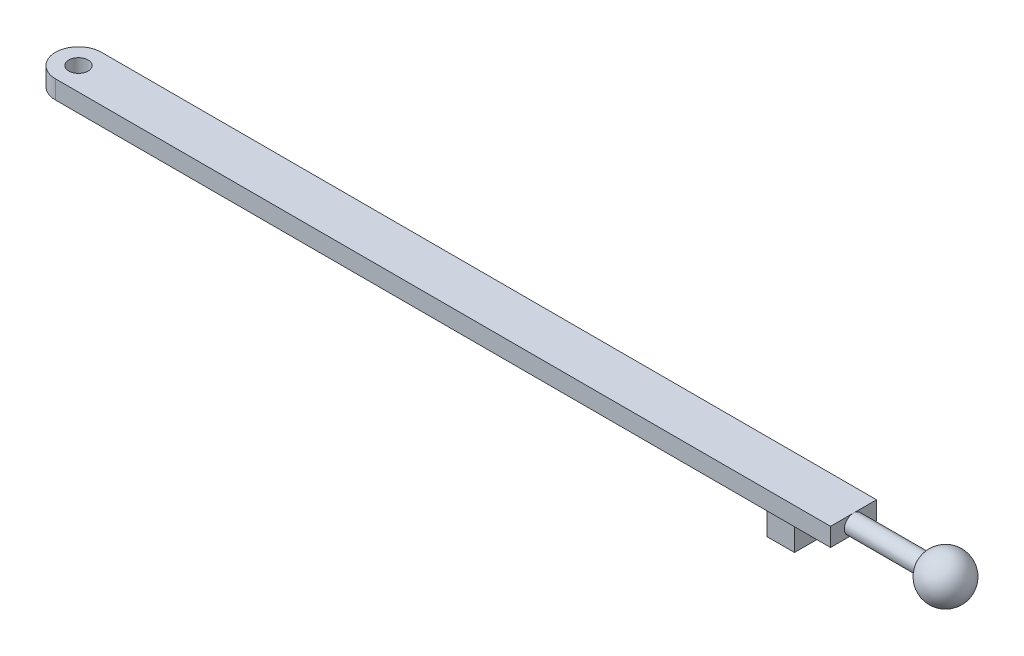
SolidWorks part; units mm, degrees
ref_plane "Front Plane" through (0, 0, 0) normal (0, 0, 1) x (1, 0, 0)
ref_plane "Top Plane" through (0, 0, 0) normal (0, 1, 0) x (1, 0, 0)
ref_plane "Right Plane" through (0, 0, 0) normal (1, 0, 0) x (0, 0, -1)
sketch "Sketch1" plane through (0, 0, 0) normal (0, 1, 0) x (1, 0, 0)
  line L0 (-10, 0) -> (0, 0) construction
  line L1 (-10, 2.5) -> (0, 2.5)
  line L2 (-10, -2.5) -> (0, -2.5)
  line L3 (0, 2.5) -> (0, -2.5)
  arc A0 (-10, 2.5) -> (-10, -2.5) centre (-10, 0) ccw
  circle A3 centre (-10, 0) radius 1
  point P3 (0, 0)
  dimension "D3" = 2
  dimension "D4" = 2.5
  dimension "D5" = 10
  dimension "D6" = 2.5
  dimension "D2" = 5
  dimension "D7" = 10
  dimension "D12" = 10
extrude "Boss-Extrude1" add sketch "Sketch1" along normal blind 2
sketch "Sketch2" plane through (0, 0, 0) normal (0, 0, 1) x (1, 0, 0)
  line L1 (0.0125, 0) -> (-0.0002, 0)
  line L5 (-10, 0) -> (0, 0) construction
  point P2 (0.0125, 1)
  dimension "D2" = 0
sketch "Sketch4" plane through (0, 0, 0) normal (1, 0, 0) x (0, 0, -1)
  circle A0 centre (0, 1) radius 1
  point P0 (0, 1)
extrude "Boss-Extrude2" add sketch "Sketch4" along normal blind 11
sketch "Sketch11" plane through (0, 0, 0) normal (0, -1, 0) x (1, 0, 0)
  line L1 (-7.9973, 0.4701) -> (-7.4489, 0.4701)
  line L2 (-7.9973, 0.4701) -> (-7.9973, -0.2612)
  line L3 (-7.9973, -0.2612) -> (-7.4489, -0.2612)
  line L4 (-7.4489, 0.4701) -> (-7.4489, -0.2612)
extrude "Boss-Extrude3" add sketch "Sketch11" along normal blind 1
sketch "Sketch12" plane through (0, -1, 0) normal (0, -1, 0) x (1, 0, 0)
  line L1 (-8.4784, 0.9317) -> (-5.4924, 0.9317)
  line L2 (-8.4784, 0.9317) -> (-8.4784, -1.8676)
  line L3 (-8.4784, -1.8676) -> (-5.4924, -1.8676)
  line L4 (-5.4924, 0.9317) -> (-5.4924, -1.8676)
extrude "Boss-Extrude4" add sketch "Sketch12" along normal blind 3
sketch "Sketch15" plane through (0, 0, 0) normal (1, 0, 0) x (0, 0, -1)
  line L1 (2.5, 0) -> (-2.5, 0)
  line L2 (2.5, 0) -> (2.5, 2)
  line L3 (2.5, 2) -> (-2.5, 2)
  line L4 (-2.5, 0) -> (-2.5, 2)
extrude "Boss-Extrude5" add sketch "Sketch15" against normal blind 86.79
sketch "Sketch16" plane through (0, 0, 0) normal (0, -1, 0) x (1, 0, 0)
  line L0 (-86.79, 0) -> (-86.79, 2.5)
  line L1 (-84.29, 5.1318) -> (-84.29, -4.4134) construction
  line L2 (-88.1253, 0) -> (-80.4547, 0) construction
  line L3 (0, -2.5) -> (-86.79, -2.5) construction
  line L4 (-84.29, 2.5) -> (-84.29, -2.5)
  line L5 (-86.79, 2.5) -> (-86.79, -2.5) construction
  line L6 (-84.29, 2.5) -> (-86.79, 2.5)
  arc A0 (-84.29, -2.5) -> (-84.29, 2.5) centre (-84.29, 0) cw
  arc A1 (-86.79, 0) -> (-84.29, 2.5) centre (-84.29, 0) cw
  point P6 (-84.29, 0)
  line M3 (0, 2.5) -> (-86.79, 2.5)
  line M4 (-86.79, 2.5) -> (-86.79, -2.5)
  line M5 (-86.79, -2.5) -> (0, -2.5)
  dimension "D1" = 2.5
  dimension "D2" = 2.5
extrude "Cut-Extrude4" cut sketch "Sketch16" against normal through all both contours A0 M5 M3 M4 region at (-86.2316, 0, -1.9416)
sketch "Sketch19" plane through (0, 2, 0) normal (0, 1, 0) x (1, 0, 0)
  circle A0 centre (-84.29, 0) radius 1.05
  dimension "D1" = 2.1
extrude "Cut-Extrude5" cut sketch "Sketch19" against normal through all both
extrude "Cut-Extrude7" cut sketch "Sketch16<4>" against normal through all both contours A0 M4 M3 region at (-86.2316, 0, 1.9416)
sketch "Sketch16<4>" plane through (0, 0, 0) normal (0, -1, 0) x (1, 0, 0) same geometry as "Sketch16"
ref_plane "Plane1" through (0, 1, 0) normal (0, -1, 0) x (-1, 0, 0)
sketch "Sketch20" plane through (0, 1, 0) normal (0, -1, 0) x (-1, 0, 0)
  line L0 (-12.5, 0) -> (-7.5, 0)
  line L1 (-11, 1) -> (-11, -1) construction
  line L2 (-11, -1) -> (0, -1) construction
  arc A0 (-7.5, 0) -> (-12.5, 0) centre (-10, 0) ccw
  dimension "D1" = 2.5
  dimension "D2" = 5
  dimension "D3" = 1
  dimension "D4" = 1
revolve "Revolve1" add sketch "Sketch20" angle 360 about L0 region at (10, 1, -1.061)
